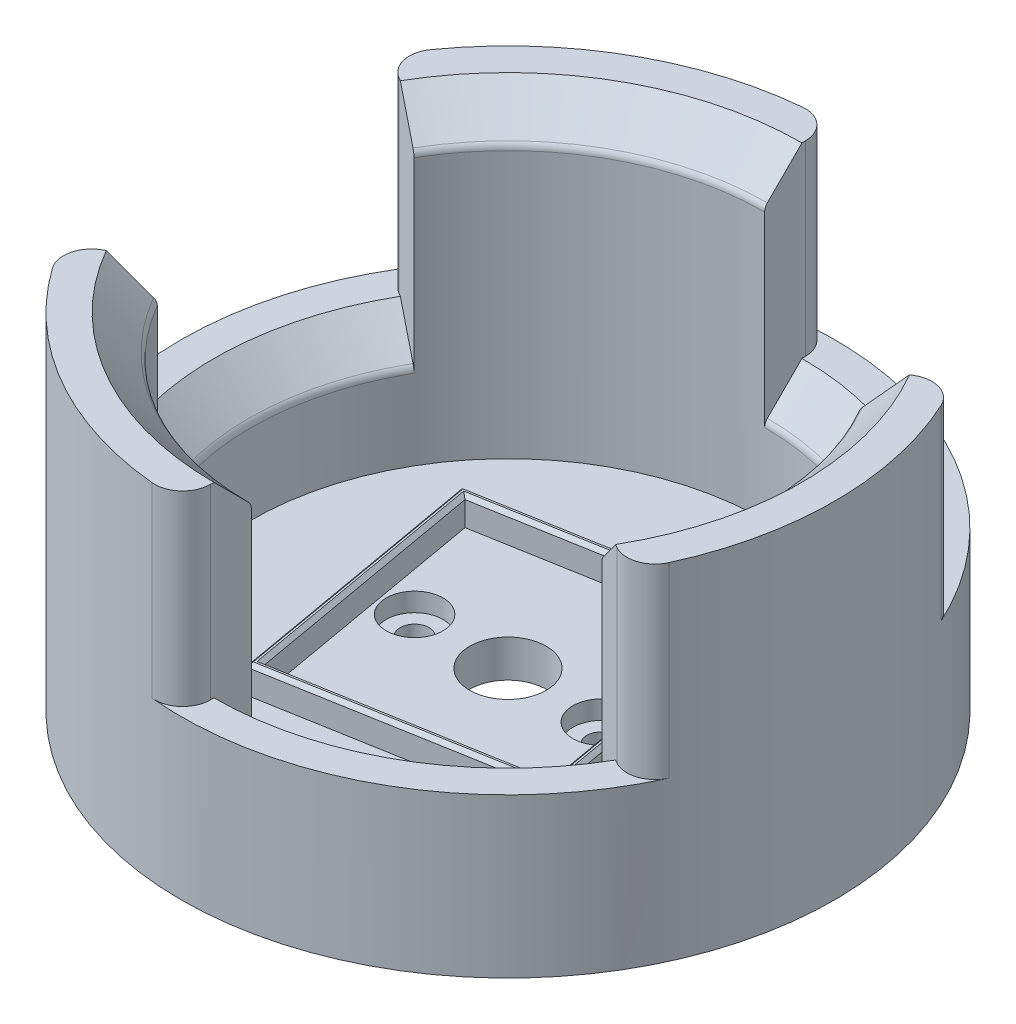
SolidWorks part; units mm, degrees
ref_plane "前视基准面" through (0, 0, 0) normal (0, 0, 1) x (1, 0, 0)
ref_plane "上视基准面" through (0, 0, 0) normal (0, 1, 0) x (1, 0, 0)
ref_plane "右视基准面" through (0, 0, 0) normal (1, 0, 0) x (0, 0, -1)
other "Configuration Table"
sketch "草图1" plane through (0, 0, 0) normal (0, 1, 0) x (1, 0, 0)
  circle A0 centre (0, 0) radius 27.5
  circle A1 centre (0, 0) radius 35
  dimension "D1" = 55
  dimension "D2" = 70
extrude "凸台-拉伸1" add sketch "草图1" along normal blind 33
extrude "凸台-拉伸2" add sketch "草图1<5>" against normal blind 4 contours A0 | A1 A0 region at (0, 0, 0) region at (-34.0101, 0, 0)
sketch "草图1<5>" plane through (0, 0, 0) normal (0, 1, 0) x (1, 0, 0) same geometry as "草图1"
chamfer "倒角1" distance 4 angle 45 1 edges at (0, 33, 27.5)
fillet "圆角1" radius 1 1 edges at (0, 29, 27.5)
sketch "草图3" plane through (0, 0, 0) normal (0, 1, 0) x (1, 0, 0)
  line L0 (0, 0) -> (10, 0)
  line L1 (0, 0) -> (0, -5.0818)
  circle A1 centre (10, 0) radius 3.05
  circle A2 centre (-10, 0) radius 3.05
  dimension "D1" = 6.1
  dimension "D2" = 10
extrude "切除-拉伸1" cut sketch "草图3" against normal blind 2 contours A2 | A1 region at (10, 0, 2.9637) region at (-10, 0, 0)
sketch "草图4" plane through (0, -2, 0) normal (0, 1, 0) x (1, 0, 0)
  circle A0 centre (-10, 0) radius 1.55
  circle A1 centre (10, 0) radius 1.55
  dimension "D1" = 3.1
extrude "切除-拉伸3" cut sketch "草图4" against normal blind 7.5
sketch "草图6" plane through (0, 0, 0) normal (0, 1, 0) x (1, 0, 0)
  circle A0 centre (0, 0) radius 4.1
  dimension "D1" = 8.2
extrude "切除-拉伸4" cut sketch "草图6" against normal blind 5
sketch "草图7" plane through (0, 0, 0) normal (0, 1, 0) x (1, 0, 0)
  line L0 (0, 0) -> (0, -35)
  line L1 (0, 0) -> (30.3109, -17.5)
  line L2 (0, 0) -> (47.8138, 0) construction
  circle A0 centre (0, 0) radius 35 construction
  arc A1 (0, -35) -> (30.3109, -17.5) centre (0, 0) ccw
  dimension "D1" = 30
  dimension "D2" = 60
extrude "切除-拉伸5" cut sketch "草图7" along normal through all from offset 13
pattern_circular "阵列(圆周)2" count 3 every 120 about axis through (0, 33, 0) along (0, -1, 0) of "切除-拉伸5"
chamfer "倒角2" distance 4 angle 45 3 edges at (13.75, 13, -23.8157) (13.75, 13, 23.8157) (-27.5, 13, 0)
fillet "圆角2" radius 1 3 edges at (13.75, 9, 23.8157) (13.75, 9, -23.8157) (-27.5, 9, 0)
fillet "圆角3" radius 3 6 edges at (-30.3109, 23, 17.5) (0, 23, 35) (30.3109, 23, 17.5) (30.3109, 23, -17.5) (-30.3109, 23, -17.5) (0, 23, -35)
sketch "草图8" plane through (0, 0, 0) normal (0, 1, 0) x (1, 0, 0)
  line L0 (-10, 0) -> (10, 0) construction
  line L1 (-15.3495, 10.7479) -> (-10.7479, -15.3495)
  line L2 (-10.7479, -15.3495) -> (15.3495, -10.7479)
  line L3 (15.3495, -10.7479) -> (10.7479, 15.3495)
  line L4 (10.7479, 15.3495) -> (-15.3495, 10.7479)
  line L5 (-15.3495, 10.7479) -> (15.3495, -10.7479) construction
  line L6 (11.559, 16.508) -> (-16.508, 11.559)
  line L7 (-16.508, 11.559) -> (-11.559, -16.508)
  line L8 (-11.559, -16.508) -> (16.508, -11.559)
  line L9 (16.508, -11.559) -> (11.559, 16.508)
  point P7 (0, 0)
  dimension "D1" = 10
  dimension "D2" = 26.5
  dimension "D3" = 28.5
extrude "凸台-拉伸3" add sketch "草图8" along normal blind 3
chamfer "倒角3" distance 0.4 angle 45 8 edges at (14.0335, 3, -2.4745) (2.4745, 3, 14.0335) (-14.0335, 3, 2.4745) (-2.4745, 3, -14.0335) (-2.3008, 3, -13.0487) (13.0487, 3, -2.3008) (2.3008, 3, 13.0487) (-13.0487, 3, 2.3008)
